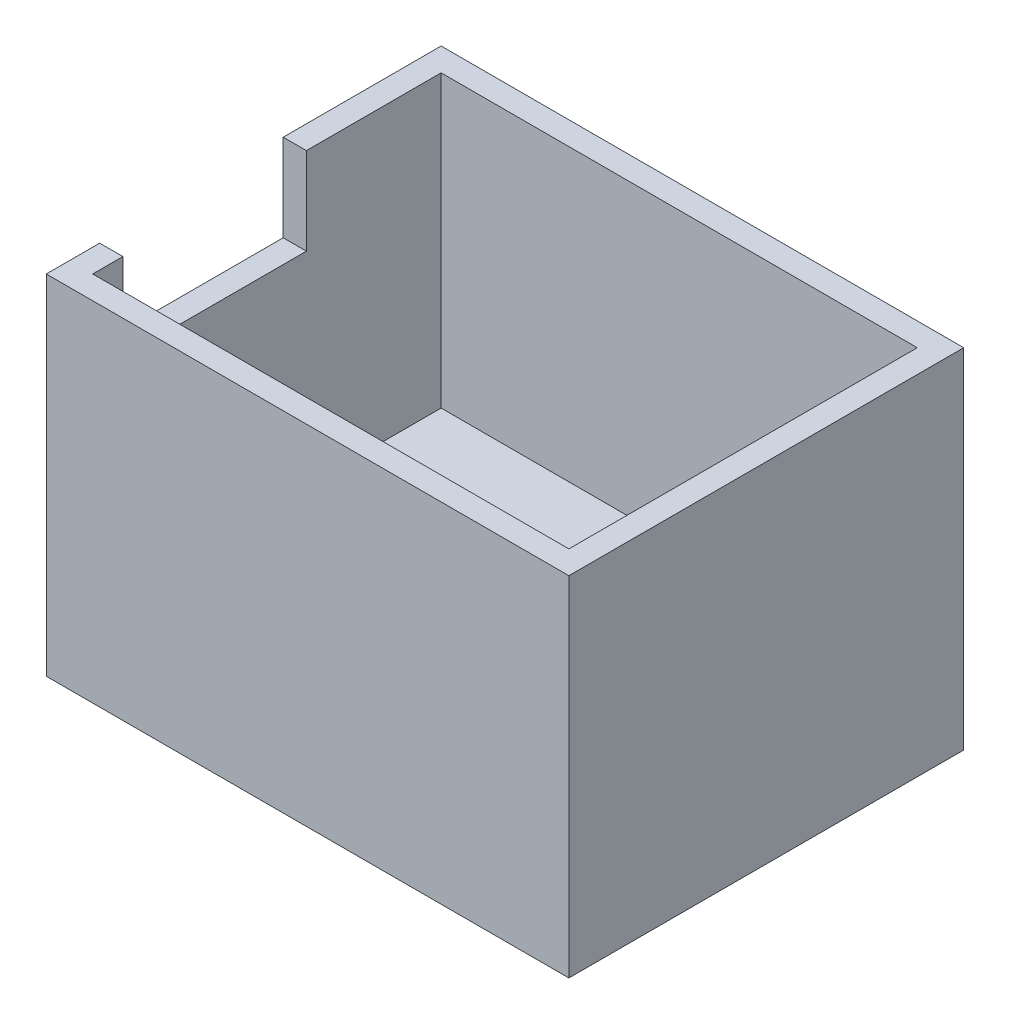
SolidWorks part; units mm, degrees
ref_plane "Front Plane" through (0, 0, 0) normal (0, 0, 1) x (1, 0, 0)
ref_plane "Top Plane" through (0, 0, 0) normal (0, 1, 0) x (1, 0, 0)
ref_plane "Right Plane" through (0, 0, 0) normal (1, 0, 0) x (0, 0, -1)
sketch "Sketch1" plane through (0, 0, 0) normal (0, 1, 0) x (1, 0, 0)
  line L1 (-28.575, -21.59) -> (28.575, -21.59)
  line L2 (-28.575, -21.59) -> (-28.575, 21.59)
  line L3 (-28.575, 21.59) -> (28.575, 21.59)
  line L4 (28.575, -21.59) -> (28.575, 21.59)
  line L5 (-28.575, -21.59) -> (28.575, 21.59) construction
  line L6 (-28.575, 21.59) -> (28.575, -21.59) construction
  point P0 (0, 0)
  dimension "D1" = 57.15
  dimension "D2" = 43.18
extrude "Boss-Extrude1" add sketch "Sketch1" along normal blind 38.1
sketch "Sketch2" plane through (0, 38.1, 0) normal (0, 1, 0) x (1, 0, 0)
  line L1 (26.035, -19.05) -> (-26.035, -19.05)
  line L2 (26.035, -19.05) -> (26.035, 19.05)
  line L3 (26.035, 19.05) -> (-26.035, 19.05)
  line L4 (-26.035, -19.05) -> (-26.035, 19.05)
  line L5 (26.035, -19.05) -> (-26.035, 19.05) construction
  line L6 (26.035, 19.05) -> (-26.035, -19.05) construction
  point P0 (0, 0)
  dimension "D1" = 38.1
  dimension "D2" = 52.07
extrude "Cut-Extrude1" cut sketch "Sketch2" against normal blind 31.75
sketch "Sketch3" plane through (0, 0, 0) normal (0, -1, 0) x (-1, 0, 0)
  line L0 (28.575, 0) -> (-28.575, 0) construction
  line L1 (7.493, -7.62) -> (-10.541, -7.62)
  line L2 (7.493, -7.62) -> (7.493, 7.62)
  line L3 (7.493, 7.62) -> (-10.541, 7.62)
  line L4 (-10.541, -7.62) -> (-10.541, 7.62)
  line L5 (7.493, -7.62) -> (-10.541, 7.62) construction
  line L6 (7.493, 7.62) -> (-10.541, -7.62) construction
  line L7 (28.575, 21.59) -> (28.575, -21.59) construction
  line L8 (-28.575, -21.59) -> (-28.575, 21.59) construction
  point P0 (-1.524, 0)
  dimension "D1" = 15.24
  dimension "D2" = 18.034
  dimension "D3" = 21.082
extrude "Cut-Extrude2" cut sketch "Sketch3" against normal through all
sketch "Sketch4" plane through (-28.575, 0, 0) normal (-1, 0, 0) x (0, 0, 1)
  line L0 (-21.59, 38.1) -> (21.59, 38.1) construction
  line L1 (15.748, 38.1) -> (-4.318, 38.1)
  line L2 (15.748, 38.1) -> (15.748, 28.575)
  line L3 (15.748, 28.575) -> (-4.318, 28.575)
  line L4 (-4.318, 38.1) -> (-4.318, 28.575)
  line L5 (21.59, 38.1) -> (21.59, 0) construction
  line L6 (-21.59, 38.1) -> (-21.59, 0) construction
  dimension "D1" = 5.842
  dimension "D2" = 17.272
  dimension "D3" = 9.525
extrude "Cut-Extrude3" cut sketch "Sketch4" against normal up to next
sketch "Sketch5" plane through (0, 0, 0) normal (0, -1, 0) x (1, 0, 0)
  line L1 (17.6249, -13.716) -> (24.2289, -13.716)
  line L2 (15.0849, -11.176) -> (15.0849, 11.176)
  line L3 (17.6249, 13.716) -> (24.2289, 13.716)
  line L4 (24.2289, -13.716) -> (24.2289, 13.716)
  line L5 (15.0849, -13.716) -> (24.2289, 13.716) construction
  line L6 (15.0849, 13.716) -> (24.2289, -13.716) construction
  arc A0 (15.0849, -11.176) -> (17.6249, -13.716) centre (17.6249, -11.176) ccw
  arc A1 (15.0849, 11.176) -> (17.6249, 13.716) centre (17.6249, 11.176) cw
  point P0 (19.6569, 0)
  dimension "D3" = 2.54
  dimension "D1" = 27.432
  dimension "D2" = 9.144
extrude "Cut-Extrude4" cut sketch "Sketch5" against normal up to next
hole_wizard "#4 Clearance Hole1" positions "Sketch7" profile "Sketch6" hole size "#4" standard "ANSI Inch" end condition through all
sketch "Sketch7" plane through (0, 0, 0) normal (0, -1, 0) x (-1, 0, 0)
  line L0 (-19.6569, 21.59) -> (-19.6569, -21.59) construction
  line L1 (-28.575, 21.59) -> (28.575, 21.59) construction
  line L2 (28.575, -21.59) -> (-28.575, -21.59) construction
  line L3 (-24.2289, 13.716) -> (-24.2289, -13.716) construction
  line L4 (-24.2289, 0) -> (-15.0849, 0) construction
  line L5 (-15.0849, -11.176) -> (-15.0849, 11.176) construction
  point P0 (-19.6569, 16.256)
  point P2 (-19.6569, -16.256)
  dimension "D1" = 4.572
  dimension "D2" = 32.512
sketch "Sketch6" plane through (19.6569, 0, -16.256) normal (1, 0, 0) x (0, 0, -1)
  line L0 (0, 0) -> (0, 38.1)
  line L1 (0, 38.1) -> (1.4732, 38.1)
  line L2 (1.4732, 38.1) -> (1.4732, 0)
  line L5 (1.4732, 0) -> (0, 0)
  line L11 (0, -6.35) -> (0, 107.95) construction
  dimension "Thru Hole Dia." = 2.9464
  dimension "Thru Hole Depth" = 38.1
hole_wizard "#6 Clearance Hole1" positions "Sketch9" profile "Sketch8" hole size "#6" standard "ANSI Inch" end condition through all
sketch "Sketch9" plane through (0, 0, 0) normal (0, -1, 0) x (-1, 0, 0)
  line L0 (3.175, -21.59) -> (3.175, 21.59) construction
  line L1 (28.575, -21.59) -> (-28.575, -21.59) construction
  line L2 (-28.575, 21.59) -> (28.575, 21.59) construction
  line L3 (28.575, 0) -> (-28.575, 0) construction
  line L4 (28.575, 21.59) -> (28.575, -21.59) construction
  line L5 (-28.575, -21.59) -> (-28.575, 21.59) construction
  point P0 (3.175, 14.605)
  point P2 (3.175, -14.605)
  dimension "D1" = 31.75
  dimension "D2" = 29.21
sketch "Sketch8" plane through (-3.175, 0, -14.605) normal (1, 0, 0) x (0, 0, -1)
  line L0 (0, 0) -> (0, 38.1)
  line L1 (0, 38.1) -> (1.8288, 38.1)
  line L2 (1.8288, 38.1) -> (1.8288, 0)
  line L5 (1.8288, 0) -> (0, 0)
  line L11 (0, -6.35) -> (0, 107.95) construction
  dimension "Thru Hole Dia." = 3.6576
  dimension "Thru Hole Depth" = 38.1
